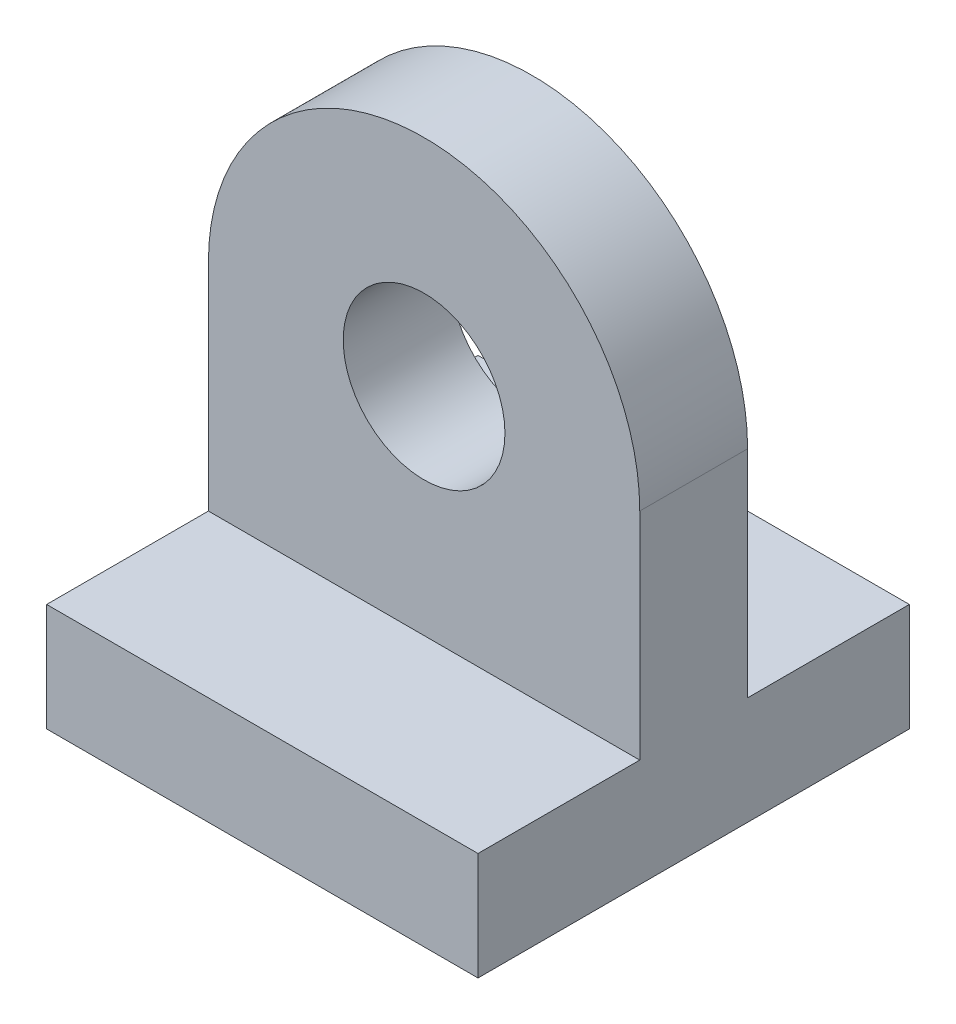
SolidWorks part; units mm, degrees
ref_plane "Front Plane" through (0, 0, 0) normal (0, 0, 1) x (1, 0, 0)
ref_plane "Top Plane" through (0, 0, 0) normal (0, 1, 0) x (1, 0, 0)
ref_plane "Right Plane" through (0, 0, 0) normal (1, 0, 0) x (0, 0, -1)
sketch "Sketch1" plane through (0, 0, 0) normal (0, 0, 1) x (1, 0, 0)
  line L2 (-8, 0) -> (-8, -12)
  line L3 (-8, -12) -> (8, -12)
  line L4 (8, 0) -> (8, -12)
  line L5 (-4.4376, 6.6564) -> (8, -12) construction
  line L6 (-8, -12) -> (4.4376, 6.6564) construction
  circle A0 centre (0, 0) radius 3
  arc A1 (8, 0) -> (-8, 0) centre (0, 0) ccw
  dimension "D1" = 6
  dimension "D2" = 8
  dimension "D3" = 12
extrude "Boss-Extrude1" add sketch "Sketch1" along normal blind 2 and the other way blind 2
sketch "Sketch2" plane through (0, 0, 0) normal (0, 0, 1) x (1, 0, 0)
  line L0 (8, -12) -> (8, 0) construction
  line L1 (-8, -12) -> (8, -12)
  line L2 (-8, -12) -> (-8, -8)
  line L3 (-8, -8) -> (8, -8)
  line L4 (8, -12) -> (8, -8)
  point P4 (-8, -8)
  point P6 (8, -3.7982)
  dimension "D1" = 4
extrude "Boss-Extrude2" add sketch "Sketch2" along normal blind 8 and the other way blind 8
